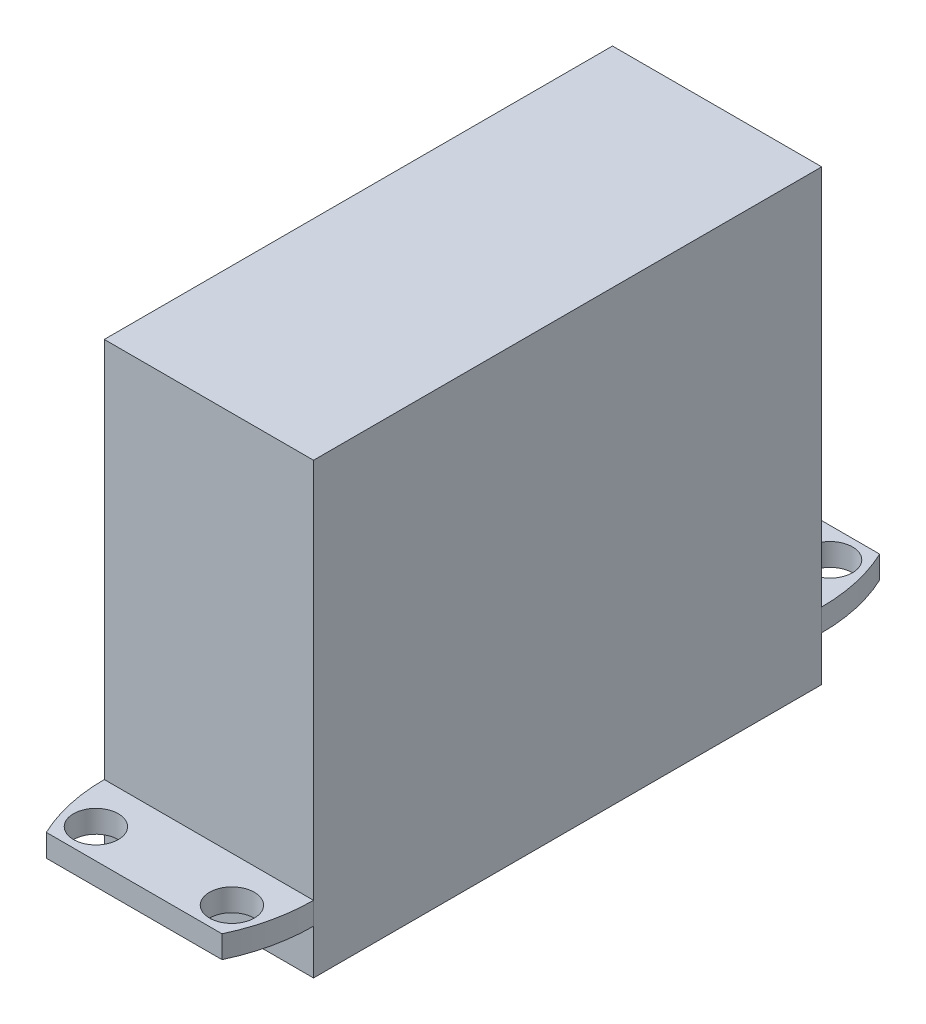
SolidWorks part; units mm, degrees
material "ABS"
ref_plane "Front Plane" through (0, 0, 0) normal (0, 0, 1) x (1, 0, 0)
ref_plane "Top Plane" through (0, 0, 0) normal (0, 1, 0) x (1, 0, 0)
ref_plane "Right Plane" through (0, 0, 0) normal (1, 0, 0) x (0, 0, -1)
sketch "Sketch1" plane through (0, 0, 0) normal (0, 1, 0) x (1, 0, 0)
  line L1 (7, -17) -> (-7, -17)
  line L2 (7, -17) -> (7, 17)
  line L3 (7, 17) -> (-7, 17)
  line L4 (-7, -17) -> (-7, 17)
  line L5 (7, -17) -> (-7, 17) construction
  line L6 (7, 17) -> (-7, -17) construction
  circle A0 centre (0, -10) radius 2.5
  point P0 (0, 0)
  dimension "D4" = 5
  dimension "D1" = 34
  dimension "D2" = 14
  dimension "D3" = 7
extrude "Boss-Extrude1" add sketch "Sketch1" along normal blind 30 contours L4 L1 L2 L3 A0 | A0 region at (0, 0, -0.4302) region at (0, 0, 10)
extrude "Cut-Extrude1" cut sketch "Sketch1<3>" along normal blind 12 contours A0
sketch "Sketch1<3>" plane through (0, 0, 0) normal (0, 1, 0) x (1, 0, 0) same geometry as "Sketch1"
sketch "Sketch4" plane through (0, 0, 0) normal (0, -1, 0) x (1, 0, 0)
  line L0 (7, 17) -> (-7, 17) construction
  line L1 (-5.8778, 22) -> (5.8778, 22)
  line L2 (7, 17) -> (7, -17) construction
  line L3 (-7, 17) -> (-7, -17) construction
  line L4 (0, 17) -> (0, 23.6968) construction
  arc A0 (-7, 17) -> (-5.8778, 22) centre (4.7, 17) cw
  arc A1 (5.8778, 22) -> (7, 17) centre (-4.7, 17) cw
  circle A2 centre (-4.55, 20.01) radius 1.5
  circle A3 centre (4.55, 20.01) radius 1.5
  point P16 (0, 22)
  line M9 (7, 17) -> (-7, 17)
  dimension "D1" = 3
  dimension "D4" = 5
  dimension "D3" = 11.7
  dimension "D2" = 3.01
  dimension "D5" = 2.45
extrude "Boss-Extrude2" add sketch "Sketch4" against normal blind 1.5 from offset 3 contours L4 L1 A0 A2 M9 | L4 A1 L1 A3 M9 region at (-2.9932, 0, 19.2732) region at (2.9932, 0, 19.2732) offset against normal yes
mirror "Mirror1" about plane through (0, 0, 0) normal (0, 0, 1) of "Boss-Extrude2"
